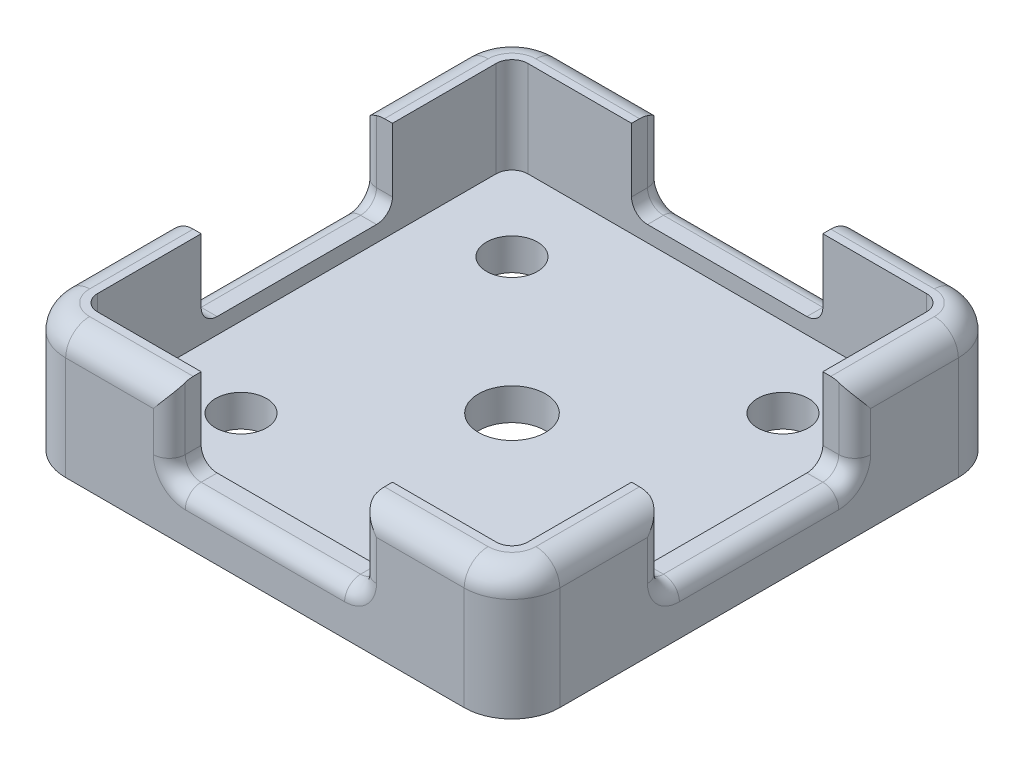
SolidWorks part; units mm, degrees
note: '?' marks a value the reader was unsure of.
ref_plane "Front Plane" through (0, 0, 0) normal (0, 0, 1) x (1, 0, 0)
ref_plane "Top Plane" through (0, 0, 0) normal (0, 1, 0) x (1, 0, 0)
ref_plane "Right Plane" through (0, 0, 0) normal (1, 0, 0) x (0, 0, -1)
sketch "Sketch1" plane through (0, 0, 0) normal (0, 1, 0) x (1, 0, 0)
  line L1 (-12.5, -15.5) -> (12.5, -15.5)
  line L2 (-15.5, -12.5) -> (-15.5, 12.5)
  line L3 (-12.5, 15.5) -> (12.5, 15.5)
  line L4 (15.5, -12.5) -> (15.5, 12.5)
  line L5 (-15.5, -15.5) -> (15.5, 15.5) construction
  line L6 (-15.5, 15.5) -> (15.5, -15.5) construction
  circle A0 centre (0, 0) radius 2.1
  circle A1 centre (-8.5, 8.5) radius 1.6
  circle A2 centre (8.5, 8.5) radius 1.6
  circle A3 centre (8.5, -8.5) radius 1.6
  circle A4 centre (-8.5, -8.5) radius 1.6
  arc A5 (-12.5, -15.5) -> (-15.5, -12.5) centre (-12.5, -12.5) cw
  arc A6 (12.5, -15.5) -> (15.5, -12.5) centre (12.5, -12.5) ccw
  arc A7 (12.5, 15.5) -> (15.5, 12.5) centre (12.5, 12.5) cw
  arc A8 (-15.5, 12.5) -> (-12.5, 15.5) centre (-12.5, 12.5) cw
  dimension "D1" = 4.2
  dimension "D2" = 3.2
  dimension "D6" = 3
  dimension "D3" = 8.5
  dimension "D5" = 31
  dimension "D4" = 4
extrude "Boss-Extrude1" add sketch "Sketch1" along normal blind 10
sketch "Sketch2" plane through (0, 10, 0) normal (0, 1, 0) x (1, 0, 0)
  line L1 (-12.5, -13.5) -> (12.5, -13.5)
  line L2 (-13.5, -12.5) -> (-13.5, 12.5)
  line L3 (-12.5, 13.5) -> (12.5, 13.5)
  line L4 (13.5, -12.5) -> (13.5, 12.5)
  line L5 (-13.5, -13.5) -> (13.5, 13.5) construction
  line L6 (-13.5, 13.5) -> (13.5, -13.5) construction
  arc A0 (12.5, 13.5) -> (13.5, 12.5) centre (12.5, 12.5) cw
  arc A1 (12.5, -13.5) -> (13.5, -12.5) centre (12.5, -12.5) ccw
  arc A2 (-12.5, -13.5) -> (-13.5, -12.5) centre (-12.5, -12.5) cw
  arc A3 (-13.5, 12.5) -> (-12.5, 13.5) centre (-12.5, 12.5) cw
  point P0 (0, 0)
  dimension "D2" = 1
  dimension "D1" = 27
extrude "Cut-Extrude1" cut sketch "Sketch2" against normal blind 8
sketch "Sketch3" plane through (0, 0, -13.5) normal (0, 0, 1) x (1, 0, 0)
  line L1 (-6, 9) -> (6, 9)
  line L2 (-6, 9) -> (-6, 3)
  line L3 (-6, 3) -> (6, 3)
  line L4 (6, 9) -> (6, 3)
  line L5 (12.5, 0) -> (-12.5, 0) construction
  line L6 (12.5, 10) -> (-12.5, 10) construction
  point P4 (-6, 8.9137)
  point P6 (0, 3)
  point P9 (0, 0)
  point P10 (0, 0)
  dimension "D1" = 12
  dimension "D2" = 6
  dimension "D3" = 1
extrude "Cut-Extrude2" cut sketch "Sketch3" against normal through all
ref_axis "Axis1" through (0, -0.5, 0) along (0, 1, 0)?
pattern_circular "CirPattern1" count 4 over 360 about axis through (0, 0, 0) along (0, 1, 0) of "Cut-Extrude2"
fillet "Fillet1" radius 1 32 edges at (-6, 9, 14.5) (6, 9, 14.5) (0, 9, 15.5) (6, 3, 14.5) (-6, 3, 14.5) (-6, 6, 15.5) (0, 3, 15.5) (6, 6, 15.5) (15.5, 9, 0) (0, 3, -15.5) (15.5, 6, 6) (15.5, 6, -6) (6, 6, -15.5) (-6, 6, -15.5) (-15.5, 9, 0) (-15.5, 6, 6) (14.5, 9, -6) (14.5, 9, 6) (14.5, 3, 6) (15.5, 3, 0) (14.5, 3, -6) (0, 9, -15.5) (6, 9, -14.5) (-6, 9, -14.5) (6, 3, -14.5) (-6, 3, -14.5) (-14.5, 9, 6) (-14.5, 9, -6) (-14.5, 3, 6) (-15.5, 3, 0) (-15.5, 6, -6) (-14.5, 3, -6)
sketch "Sketch4" plane through (0, 0, 0) normal (1, 0, 0) x (0, 0, -1)
  line L0 (12.5, 10) -> (5, 10) construction
  line L1 (34.9186, 8) -> (-30.0088, 8)
  line L2 (34.9186, 8) -> (34.9186, 10)
  line L3 (34.9186, 10) -> (-30.0088, 10)
  line L4 (-30.0088, 8) -> (-30.0088, 10)
  line L5 (34.9186, 8) -> (-30.0088, 10) construction
  line L6 (34.9186, 10) -> (-30.0088, 8) construction
  point P0 (2.4549, 9)
  dimension "D1" = 2
extrude "Cut-Extrude3" cut sketch "Sketch4" against normal through all both and the other way through all
fillet "Fillet2" radius 1.5 12 edges at (14.6213, 8, -14.6213) (9.75, 8, -15.5) (15.5, 8, -9.75) (15.5, 8, 9.75) (14.6213, 8, 14.6213) (9.75, 8, 15.5) (-9.75, 8, 15.5) (-14.6213, 8, 14.6213) (-15.5, 8, 9.75) (-9.75, 8, -15.5) (-15.5, 8, -9.75) (-14.6213, 8, -14.6213)
